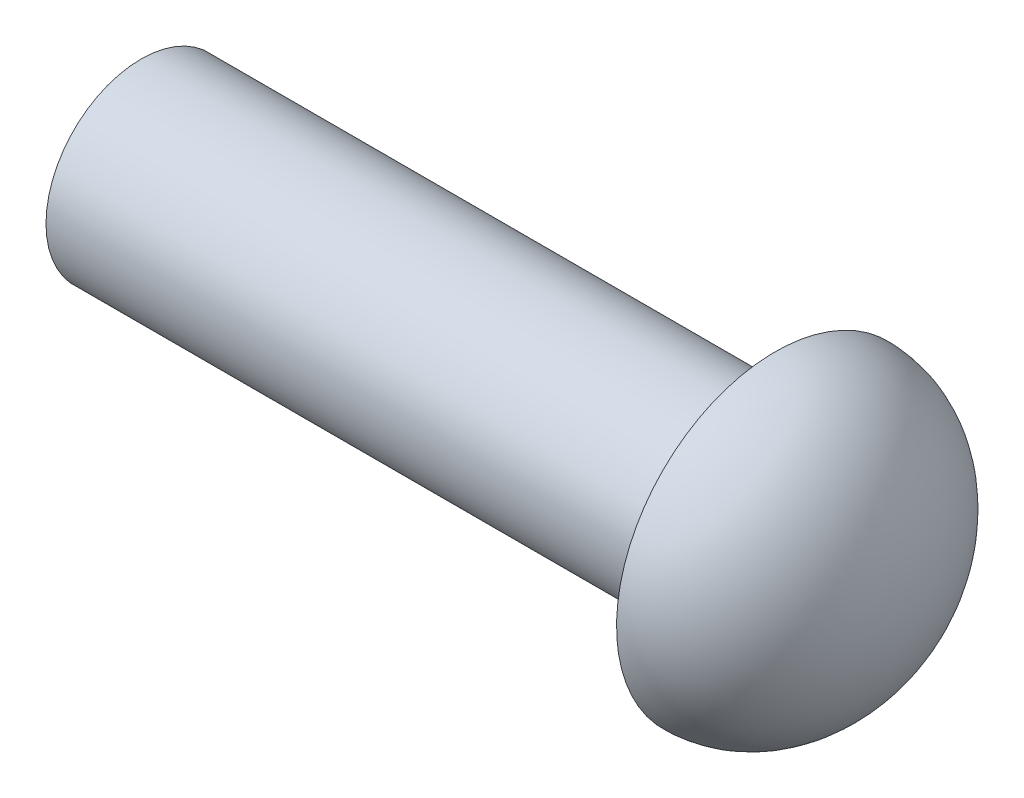
SolidWorks part; units mm, degrees
ref_plane "Front Plane" through (0, 0, 0) normal (0, 0, 1) x (1, 0, 0)
ref_plane "Top Plane" through (0, 0, 0) normal (0, 1, 0) x (1, 0, 0)
ref_plane "Right Plane" through (0, 0, 0) normal (1, 0, 0) x (0, 0, -1)
sketch "Sketch1" plane through (0, 0, 0) normal (0, 0, 1) x (1, 0, 0)
  line L0 (0, 0) -> (0, -1.5)
  line L1 (0, -1.5) -> (10, -1.5)
  line L2 (10, -1.5) -> (10, -2.5)
  line L5 (12, 0) -> (0, 0)
  ellipse E0 centre (10, 0) end of major axis (10, -2.5) minor radius 2 (10, -2.5) -> (12, 0) ccw
  point P6 (0, 0)
  point P8 (6.9166, 3.1445)
  point P9 (0, 0)
  point P14 (8.6915, 2.7219)
  point P15 (7.169, 0)
  point P16 (0, 0)
  point P17 (0, 0)
  dimension "D1" = 10
  dimension "D2" = 2
  dimension "D3" = 2.5
  dimension "D4" = 1.5
revolve "Revolve1" add sketch "Sketch1" angle 360 about L5
